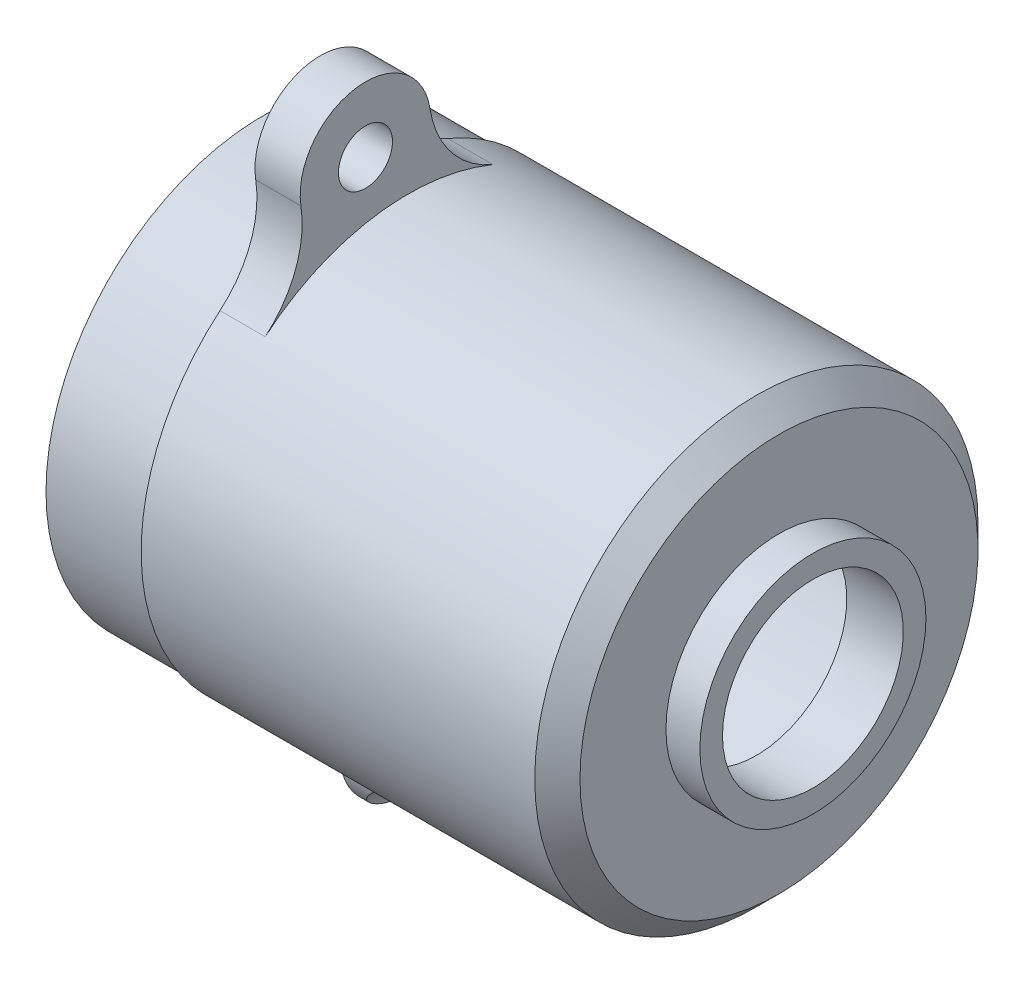
SolidWorks part; units mm, degrees
material "6061-T6 (SS)"
ref_plane "Front Plane" through (0, 0, 0) normal (0, 0, 1) x (1, 0, 0)
ref_plane "Top Plane" through (0, 0, 0) normal (0, 1, 0) x (1, 0, 0)
ref_plane "Right Plane" through (0, 0, 0) normal (1, 0, 0) x (0, 0, -1)
other "Center of Mass"
sketch "Sketch1" plane through (-31.75, 0, 0) normal (1, 0, 0) x (0, 0, -1)
  line L0 (0, 0) -> (-2.9885, 19.3009) construction
  line L1 (-0.1168, 15.7295) -> (1.5403, 20.0021) construction
  line L2 (1.5403, 20.0021) -> (-1.3314, 23.5735) construction
  line L3 (-1.3314, 23.5735) -> (-5.8601, 22.8723) construction
  line L4 (-5.8601, 22.8723) -> (-7.5172, 18.5996) construction
  line L5 (-7.5172, 18.5996) -> (-4.6456, 15.0282) construction
  line L6 (-4.6456, 15.0282) -> (-0.1168, 15.7295) construction
  line L7 (4.6456, -15.0282) -> (0.1168, -15.7295) construction
  line L8 (0.1168, -15.7295) -> (-1.5403, -20.0021) construction
  line L9 (-1.5403, -20.0021) -> (1.3314, -23.5735) construction
  line L10 (1.3314, -23.5735) -> (5.8601, -22.8723) construction
  line L11 (5.8601, -22.8723) -> (7.5172, -18.5996) construction
  line L12 (7.5172, -18.5996) -> (4.6456, -15.0282) construction
  line L13 (-7.5172, 18.5996) -> (1.5403, 20.0021) construction
  line L15 (0, 0) -> (12.0771, 1.87) construction
  circle A0 centre (0, 0) radius 13.9746
  circle A1 centre (0, 0) radius 15.5621 construction
  circle A3 centre (2.9885, -19.3009) radius 3.9688 construction
  circle A4 centre (-2.9885, 19.3009) radius 8.7404 construction
  arc A8 (-10.0273, 11.901) -> (-5.9586, -14.3762) centre (0, 0) ccw
  arc A9 (5.9586, 14.3762) -> (10.0273, -11.901) centre (0, 0) cw
  circle A16 centre (-2.9885, 19.3009) radius 2.667 construction
  circle A17 centre (2.9885, -19.3009) radius 2.667 construction
  arc A18 (-9.6776, 36.4316) -> (-11.4522, 23.3267) centre (127.0686, 11.2409) ccw construction
  arc A19 (4.4842, 36.4316) -> (4.6179, 28.7559) centre (76.9988, 33.8561) ccw construction
  arc A20 (-10.0273, 11.901) -> (-7.5172, 18.5996) centre (-14.7303, 17.4828) ccw
  arc A21 (-7.5172, 18.5996) -> (1.5403, 20.0021) centre (-2.9885, 19.3009) cw
  arc A22 (1.5403, 20.0021) -> (5.9586, 14.3762) centre (8.7533, 21.1189) ccw
  arc A23 (7.5172, -18.5996) -> (10.0273, -11.901) centre (14.7303, -17.4828) cw
  arc A24 (-1.5403, -20.0021) -> (7.5172, -18.5996) centre (2.9885, -19.3009) ccw
  arc A25 (-5.9586, -14.3762) -> (-1.5403, -20.0021) centre (-8.7533, -21.1189) cw
  point P4 (-2.3812, 15.3788)
  dimension "D1" = 27.9492
  dimension "D4" = 5.334
  dimension "D2" = 1.5875
  dimension "D3" = 7.9375
extrude "Boss-Extrude1" add sketch "Sketch1" along normal blind 3.175
sketch "Sketch2" plane through (-28.575, 0, 0) normal (1, 0, 0) x (0, 0, -1)
  circle A0 centre (0, 0) radius 13.9746
  circle A1 centre (0, 0) radius 15.5621
  arc A2 (-10.0273, 11.901) -> (-5.9586, -14.3762) centre (0, 0) ccw construction
  circle A3 centre (0, 0) radius 13.9746 construction
extrude "Boss-Extrude2" add sketch "Sketch2" along normal up to surface (24.4625 mm away)
sketch "Sketch5" plane through (0, 0, 0) normal (0, 0, 1) x (1, 0, 0)
  line L1 (-0.1437, 7.9375) -> (-0.1437, 6.35)
  line L3 (-4.1125, -15.5621) -> (-4.1125, 15.5621) construction
  line L4 (-4.1125, 6.35) -> (-4.1125, 15.5621)
  line L5 (0, 0) -> (45.5597, 0) construction
  line L6 (-4.1125, 6.35) -> (-0.1437, 6.35)
  line L9 (-0.1437, 7.9375) -> (-2.525, 7.9375)
  line L10 (-2.525, 7.9375) -> (-2.525, 13.9746)
  line L11 (-2.525, 13.9746) -> (-4.1125, 15.5621)
  dimension "D2" = 3.9688
  dimension "D1" = 12.7
  dimension "D3" = 1.5875
  dimension "D4" = 1.5875
  dimension "D5" = 45
revolve "Revolve1" add sketch "Sketch5" angle 360 about L5
sketch "Sketch3" plane through (-31.75, 0, 0) normal (-1, 0, 0) x (0, 0, 1)
  circle A0 centre (0, 0) radius 13.9746
  circle A1 centre (0, 0) radius 15.2446
  circle A2 centre (0, 0) radius 13.9746 construction
  dimension "D1" = 1.27
extrude "Boss-Extrude3" add sketch "Sketch3" along normal blind 7
sketch "Sketch6" plane through (0, 0, 0) normal (0, 0, 1) x (1, 0, 0)
  line L0 (-31.75, -23.8836) -> (-31.5663, -23.8836)
  line L1 (-31.75, -23.8836) -> (-28.575, -23.8836) construction
  line L2 (-31.75, -23.8836) -> (-31.75, -25.4)
  line L3 (-31.75, -18.5996) -> (-31.75, -23.8836) construction
  arc A0 (-31.75, -25.4) -> (-31.4083, -27.455) centre (-25.4, -25.4) ccw construction
  arc A1 (-31.5663, -23.8836) -> (-31.75, -25.4) centre (-25.4, -25.4) cw
extrude "Cut-Extrude1" cut sketch "Sketch6" against normal through all both and the other way through all
hole_wizard "#6 Clearance Hole1" positions "Sketch7" profile "Sketch8" hole size "#6" standard "ANSI Inch" end condition up to next
sketch "Sketch7" plane through (-28.575, 0, 0) normal (1, 0, 0) x (0, 0, -1)
  point P0 (-2.9885, 19.3009)
  point P3 (2.9885, -19.3009)
sketch "Sketch8" plane through (-28.575, 19.3009, 2.9885) normal (0, 1, 0) x (0, 0, -1)
  line L0 (0, 0) -> (0, 3.175)
  line L1 (0, 3.175) -> (1.8986, 3.175)
  line L2 (1.8986, 3.175) -> (1.8986, 0)
  line L5 (1.8986, 0) -> (0, 0)
  line L11 (0, -6.35) -> (0, 107.95) construction
  dimension "Thru Hole Dia." = 3.7973
  dimension "Thru Hole Depth" = 3.175
equation "\"motor diameter\"= 28mm"
equation "\"D1@Sketch1\"=\"motor diameter\"-0.002in"
equation "\"D1@Boss-Extrude3\"=7mm"
equation "\"D2@Sketch5\"=5/32"
